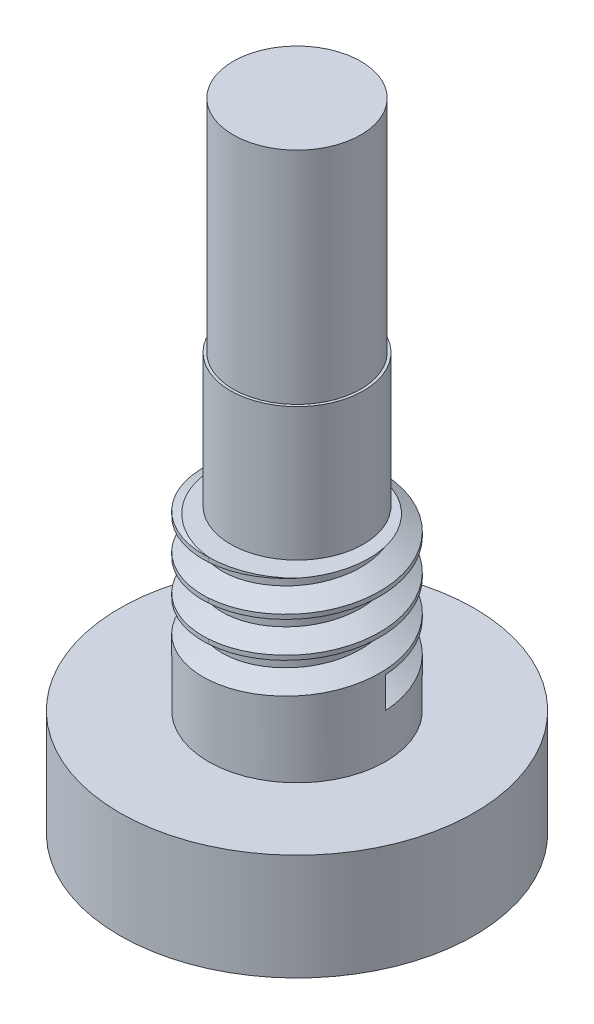
SolidWorks part; units mm, degrees
ref_plane "Front Plane" through (0, 0, 0) normal (0, 0, 1) x (1, 0, 0)
ref_plane "Top Plane" through (0, 0, 0) normal (0, 1, 0) x (1, 0, 0)
ref_plane "Right Plane" through (0, 0, 0) normal (1, 0, 0) x (0, 0, -1)
sketch "Sketch1" plane through (0, 0, 0) normal (0, 1, 0) x (1, 0, 0)
  circle A0 centre (0, 0) radius 2.286
  dimension "D1" = 4.572
extrude "Boss-Extrude1" add sketch "Sketch1" along normal blind 7.8892
sketch "Sketch2" plane through (0, 0, 0) normal (0, -1, 0) x (-1, 0, 0)
  circle A0 centre (0, 0) radius 2.3825
  dimension "D1" = 4.765
extrude "Boss-Extrude2" add sketch "Sketch2" along normal blind 4.7622
sketch "Sketch3" plane through (0, -4.7622, 0) normal (0, -1, 0) x (-1, 0, 0)
  circle A0 centre (0, 0) radius 3.175
  dimension "D1" = 6.35
extrude "Boss-Extrude3" add sketch "Sketch3" along normal blind 3.175
sketch "Sketch4" plane through (0, -7.9372, 0) normal (0, -1, 0) x (-1, 0, 0)
  circle A0 centre (0, 0) radius 3.175
  dimension "D1" = 6.35
extrude "Boss-Extrude4" add sketch "Sketch4" along normal blind 3.175
thread "Thread2" pitch 1.27 method cut profile "Thread Profile3" start angle 0, offset 1.5875, length 0, pitch 1.27, diameter 6.35
ref_plane "Plane3" through (3.175, -9.5247, 0) normal (0, 0, 1) x (1, 0, 0)
sketch "Thread Profile3" plane through (3.175, -9.5247, 0) normal (0, 0, 1) x (1, 0, 0)
  line L0 (0, 0) -> (0, 1.27) construction
  line L11 (0, 0) -> (0, 1.1112)
  line L12 (0, 1.1112) -> (-0.6874, 0.7144)
  line L13 (-0.6874, 0.7144) -> (-0.6874, 0.3969)
  line L15 (-0.6874, 0.3969) -> (0, 0)
  line L17 (-0.6874, 0.5556) -> (0, 0.5556) construction
  point P2 (0, 0)
  dimension "Pitch" = 1.27
  dimension "Profile_Angle" = 60
  dimension "Profile_Land" = 0.3175
  dimension "Profile_Height" = 0.6874
sketch "Sketch11" plane through (0, -11.1122, 0) normal (0, -1, 0) x (-1, 0, 0)
  circle A0 centre (0, 0) radius 6.35
  dimension "D1" = 12.7
extrude "Boss-Extrude5" add sketch "Sketch11" along normal blind 3.81
fillet "Fillet1" [suppressed] radius 2.54
